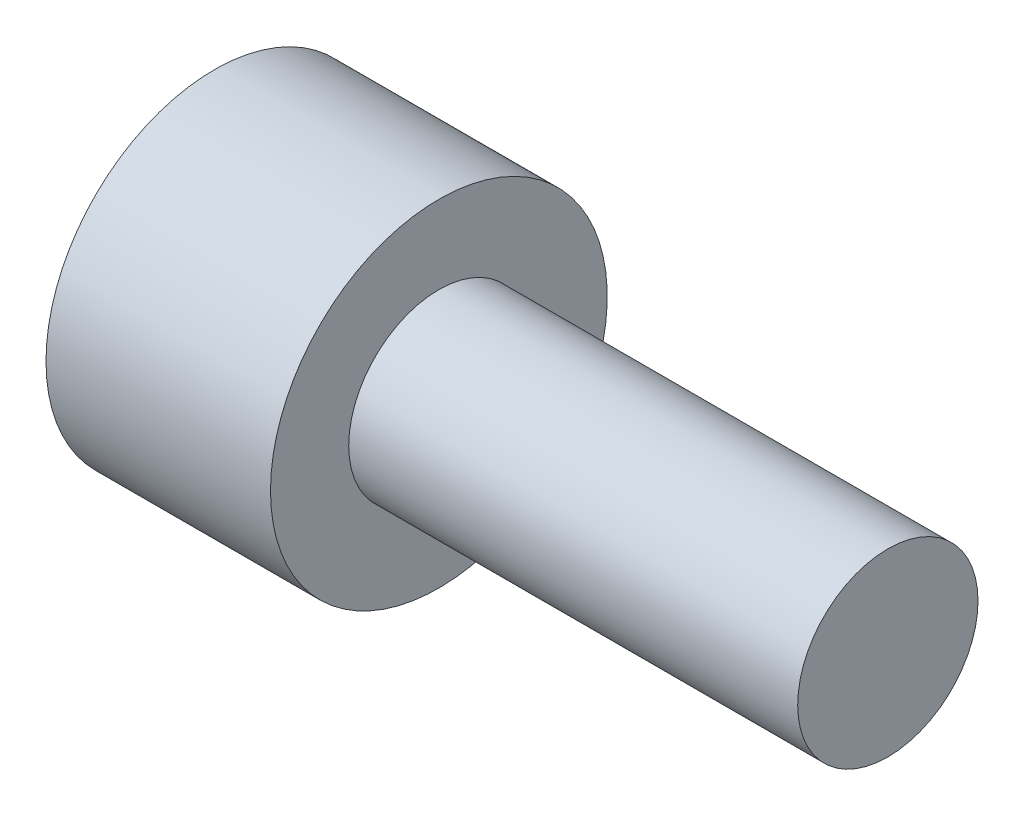
SolidWorks part; units mm, degrees
ref_plane "Front Plane" through (0, 0, 0) normal (0, 0, 1) x (1, 0, 0)
ref_plane "Top Plane" through (0, 0, 0) normal (0, 1, 0) x (1, 0, 0)
ref_plane "Right Plane" through (0, 0, 0) normal (1, 0, 0) x (0, 0, -1)
sketch "Screw Sketch" plane through (0, 0, 0) normal (0, 0, 1) x (1, 0, 0)
  line L0 (-1000, 0) -> (1000, 0) construction
  line L1 (-6.35, 0) -> (-6.35, 4.7625)
  line L2 (-6.35, 4.7625) -> (0, 4.7625)
  line L3 (0, 4.7625) -> (0, 2.55)
  line L4 (0, 2.55) -> (12.7, 2.55)
  line L5 (12.7, 2.55) -> (12.7, 0)
  line L6 (12.7, 0) -> (-6.35, 0)
revolve "Screw" add sketch "Screw Sketch" angle 360 about L0
ref_axis "Engine Axis" through (13.6525, 0, 0) along (-1, 0, 0)
ref_plane "Head Top" through (-6.35, 0, 0) normal (1, 0, 0) x (0, 0, -1)
sketch "Socket Sketch" plane through (-6.35, 0, 0) normal (1, 0, 0) x (0, 0, -1)
  line L0 (2.7482, 0) -> (1.3741, 2.38)
  line L1 (1.3741, 2.38) -> (-1.3741, 2.38)
  line L2 (-1.3741, 2.38) -> (-2.7482, 0)
  line L3 (-2.7482, 0) -> (-1.3741, -2.38)
  line L4 (-1.3741, -2.38) -> (1.3741, -2.38)
  line L5 (1.3741, -2.38) -> (2.7482, 0)
extrude "Socket" cut sketch "Socket Sketch" along normal blind 3.175
